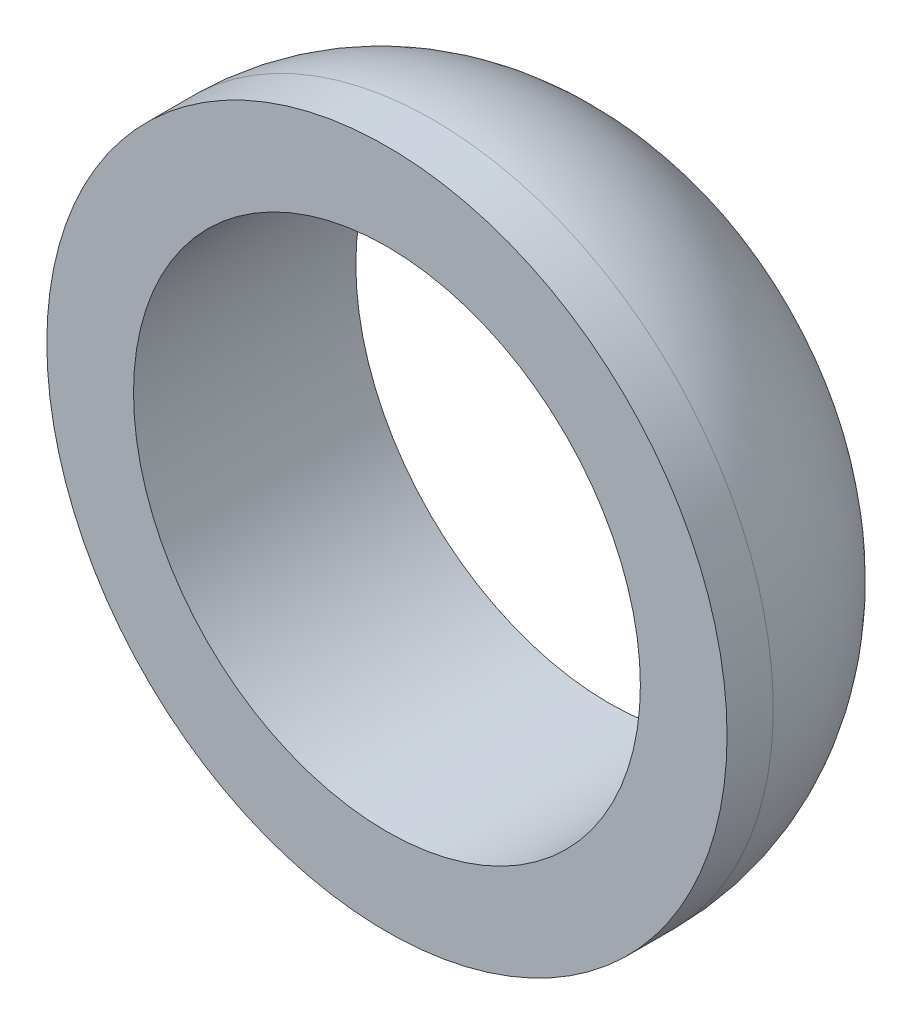
SolidWorks part; units mm, degrees
material "Plain Carbon Steel"
ref_plane "Front" through (0, 0, 0) normal (0, 0, 1) x (1, 0, 0)
ref_plane "Top" through (0, 0, 0) normal (0, 1, 0) x (1, 0, 0)
ref_plane "Right" through (0, 0, 0) normal (1, 0, 0) x (0, 0, -1)
sketch "Sketch2" plane through (0, 0, 0) normal (0, 0, 1) x (1, 0, 0)
  circle A0 centre (-9.8411, 7.9927) radius 19.431
  dimension "D1" = 38.862
extrude "Boss-Extrude1" add sketch "Sketch2" along normal blind 12.7
sketch "Sketch4" plane through (0, 0, 0) normal (0, 0, -1) x (-1, 0, 0)
  circle A0 centre (9.8411, 7.9927) radius 14.478
  dimension "D1" = 28.956
extrude "Cut-Extrude1" cut sketch "Sketch4" against normal blind 12.7
fillet "Fillet2" radius 12.7 1 edges at (9.5899, 7.9927, 0)
